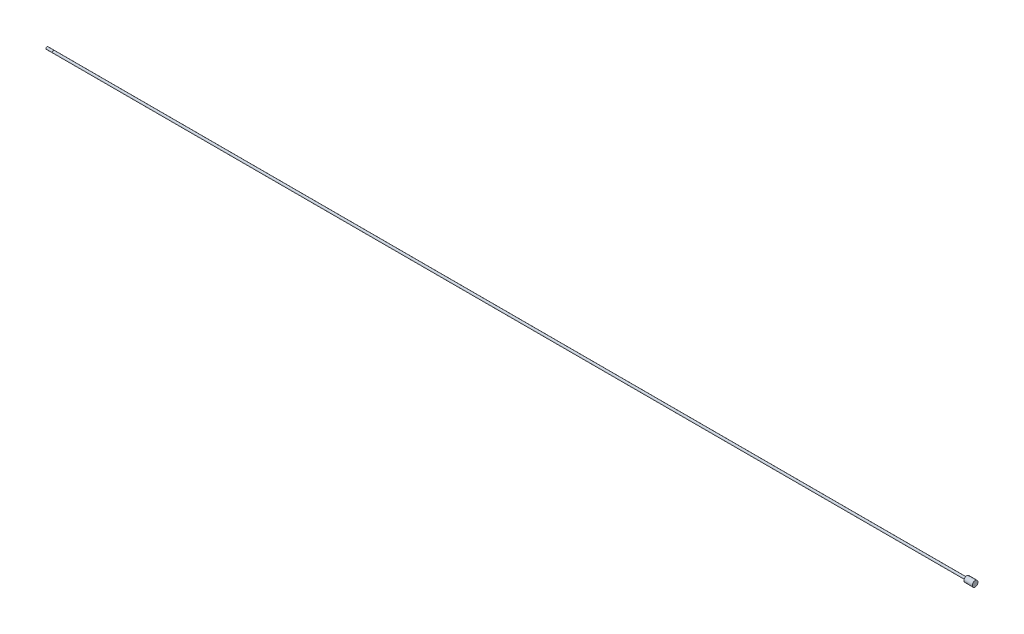
SolidWorks part; units mm, degrees
material "Plain Carbon Steel"
ref_plane "Front Plane" through (0, 0, 0) normal (0, 0, 1) x (1, 0, 0)
ref_plane "Top Plane" through (0, 0, 0) normal (0, 1, 0) x (1, 0, 0)
ref_plane "Right Plane" through (0, 0, 0) normal (1, 0, 0) x (0, 0, -1)
sketch "Sketch1" plane through (0, 0, 0) normal (0, 0, 1) x (1, 0, 0)
  line L0 (0, 0) -> (0, 1.5875)
  line L1 (0, 1.5875) -> (1291.463, 1.5875)
  line L2 (1291.463, 1.5875) -> (1291.463, 4.0323)
  line L3 (1291.463, 4.0323) -> (1303.2994, 4.0323)
  line L4 (1303.2994, 4.0323) -> (1303.2994, 0)
  line L5 (1303.2994, 0) -> (0, 0)
  line L6 (1303.2994, 0) -> (0, 0) construction
revolve "Revolve1" add sketch "Sketch1" angle 360 about L6 reverse direction yes
cosmetic thread "Cosmetic Thread1" parameters "D1"=9.652, "D2"=2.4181
sketch "Sketch2" plane through (0, 0, 0) normal (0, 0, 1) x (1, 0, 0)
  line L0 (-9.652, 0) -> (-9.652, 1.209)
  line L1 (-9.652, 1.209) -> (-9.2735, 1.5875)
  line L2 (-9.2735, 1.5875) -> (0, 1.5875)
  line L3 (0, 1.5875) -> (0, 0)
  line L4 (0, 0) -> (-9.652, 0)
  line L5 (0, 0) -> (-9.652, 0) construction
revolve "Revolve2" add sketch "Sketch2" angle 360 about L5 reverse direction yes
ref_plane "Plane1" through (0, 0, 0) normal (1, 0, 0) x (0, 0, -1)
ref_plane "Plane2" through (0, 0, 0) normal (1, 0, 0) x (0, 0, -1)
ref_plane "Plane3" through (2594.7624, 0, 0) normal (1, 0, 0) x (0, 0, -1)
ref_plane "Plane4" through (-9.652, 0, 0) normal (1, 0, 0) x (0, 0, -1)
sketch "Sketch3" plane through (0, 0, 0) normal (0, 0, 1) x (1, 0, 0)
  line L0 (-0.254, 1.8415) -> (-0.254, 1.3335)
  line L1 (-0.254, 1.3335) -> (0, 1.3335)
  line L2 (0, 1.3335) -> (0, 1.8415)
  line L3 (0, 1.8415) -> (-0.254, 1.8415)
  line L4 (0, 0) -> (-0.254, 0) construction
revolve "Cut-Revolve1" cut sketch "Sketch3" angle 360 about L4 reverse direction yes
ref_plane "Plane5" through (0, 0, 0) normal (1, 0, 0) x (0, 0, -1)
ref_plane "Plane6" through (0, 0, 0) normal (1, 0, 0) x (0, 0, -1)
ref_plane "Plane7" through (-9.652, 0, 0) normal (1, 0, 0) x (0, 0, -1)
ref_plane "dia1 XY" through (0, 0, 0) normal (1, 0, 0) x (0, 0, -1)
ref_plane "dia1 XZ" through (0, 1.5875, 0) normal (0, -1, 0) x (-1, 0, 0)
ref_plane "dia1 YZ" through (0, 0, 0) normal (0, 0, -1) x (-1, 0, 0)
ref_axis "dia1 X" through (0, 1.5875, 80.9) along (0, 0, -1)
ref_axis "dia1 Y" through (0, -50, 0) along (0, 1, 0)
ref_axis "dia1 Z" through (80.9, 1.5875, 0) along (-1, 0, 0)
sketch3d "dia1"
  point P0 (0, 1.5875, 0)
ref_plane "dia12 XY" through (0, 0, 0) normal (1, 0, 0) x (0, 0, -1)
ref_plane "dia12 XZ" through (0, 0, 0) normal (0, -1, 0) x (-1, 0, 0)
ref_plane "dia12 YZ" through (0, 0, 7.6835) normal (0, 0, -1) x (-1, 0, 0)
ref_axis "dia12 X" through (0, 0, 80.9) along (0, 0, -1)
ref_axis "dia12 Y" through (0, -50, 7.6835) along (0, 1, 0)
ref_axis "dia12 Z" through (80.9, 0, 7.6835) along (-1, 0, 0)
sketch3d "dia12"
  point P0 (0, 0, 7.6835)
ref_plane "dia1r XY" through (0, 0, 0) normal (1, 0, 0) x (0, 0, -1)
ref_plane "dia1r XZ" through (0, 0, 0) normal (0, -1, 0) x (-1, 0, 0)
ref_plane "dia1r YZ" through (0, 0, 5.5626) normal (0, 0, -1) x (-1, 0, 0)
ref_axis "dia1r X" through (0, 0, 80.9) along (0, 0, -1)
ref_axis "dia1r Y" through (0, -50, 5.5626) along (0, 1, 0)
ref_axis "dia1r Z" through (80.9, 0, 5.5626) along (-1, 0, 0)
sketch3d "dia1r"
  point P0 (0, 0, 5.5626)
ref_plane "dia2 XY" through (0, 0, 0) normal (1, 0, 0) x (0, 0, -1)
ref_plane "dia2 XZ" through (0, -1.5875, 0) normal (0, -1, 0) x (-1, 0, 0)
ref_plane "dia2 YZ" through (0, 0, 0) normal (0, 0, -1) x (-1, 0, 0)
ref_axis "dia2 X" through (0, -1.5875, 80.9) along (0, 0, -1)
ref_axis "dia2 Y" through (0, -50, 0) along (0, 1, 0)
ref_axis "dia2 Z" through (80.9, -1.5875, 0) along (-1, 0, 0)
sketch3d "dia2"
  point P0 (0, -1.5875, 0)
ref_plane "dia22 XY" through (0, 0, 0) normal (1, 0, 0) x (0, 0, -1)
ref_plane "dia22 XZ" through (0, 0, 0) normal (0, -1, 0) x (-1, 0, 0)
ref_plane "dia22 YZ" through (0, 0, -7.6835) normal (0, 0, -1) x (-1, 0, 0)
ref_axis "dia22 X" through (0, 0, 80.9) along (0, 0, -1)
ref_axis "dia22 Y" through (0, -50, -7.6835) along (0, 1, 0)
ref_axis "dia22 Z" through (80.9, 0, -7.6835) along (-1, 0, 0)
sketch3d "dia22"
  point P0 (0, 0, -7.6835)
ref_plane "dia2r XY" through (0, 0, 0) normal (1, 0, 0) x (0, 0, -1)
ref_plane "dia2r XZ" through (0, 0, 0) normal (0, -1, 0) x (-1, 0, 0)
ref_plane "dia2r YZ" through (0, 0, -5.5626) normal (0, 0, -1) x (-1, 0, 0)
ref_axis "dia2r X" through (0, 0, 80.9) along (0, 0, -1)
ref_axis "dia2r Y" through (0, -50, -5.5626) along (0, 1, 0)
ref_axis "dia2r Z" through (80.9, 0, -5.5626) along (-1, 0, 0)
sketch3d "dia2r"
  point P0 (0, 0, -5.5626)
ref_plane "rl1 XY" through (-9.652, 0, 0) normal (1, 0, 0) x (0, 0, -1)
ref_plane "rl1 XZ" through (0, 0, 0) normal (0, -1, 0) x (-1, 0, 0)
ref_plane "rl1 YZ" through (0, 0, 0) normal (0, 0, -1) x (-1, 0, 0)
ref_axis "rl1 X" through (-9.652, 0, 80.9) along (0, 0, -1)
ref_axis "rl1 Y" through (-9.652, -50, 0) along (0, 1, 0)
ref_axis "rl1 Z" through (80.9, 0, 0) along (-1, 0, 0)
sketch3d "rl1"
  point P0 (-9.652, 0, 0)
ref_plane "rl2 XY" through (0, 0, 0) normal (1, 0, 0) x (0, 0, -1)
ref_plane "rl2 XZ" through (0, 0, 0) normal (0, -1, 0) x (-1, 0, 0)
ref_plane "rl2 YZ" through (0, 0, 0) normal (0, 0, -1) x (-1, 0, 0)
ref_axis "rl2 X" through (0, 0, 80.9) along (0, 0, -1)
ref_axis "rl2 Y" through (0, -50, 0) along (0, 1, 0)
ref_axis "rl2 Z" through (80.9, 0, 0) along (-1, 0, 0)
sketch3d "rl2"
  point P0 (0, 0, 0)
ref_plane "rod_cp XY" through (0, 0, 0) normal (1, 0, 0) x (0, 0, -1)
ref_plane "rod_cp XZ" through (0, 0, 0) normal (0, -1, 0) x (-1, 0, 0)
ref_plane "rod_cp YZ" through (0, 0, 0) normal (0, 0, -1) x (-1, 0, 0)
ref_axis "rod_cp X" through (0, 0, 80.9) along (0, 0, -1)
ref_axis "rod_cp Y" through (0, -50, 0) along (0, 1, 0)
ref_axis "rod_cp Z" through (80.9, 0, 0) along (-1, 0, 0)
sketch3d "rod_cp"
  point P0 (0, 0, 0)
ref_plane "thd1 XY" through (-9.652, 0, 0) normal (1, 0, 0) x (0, 0, -1)
ref_plane "thd1 XZ" through (0, 1.5875, 0) normal (0, -1, 0) x (-1, 0, 0)
ref_plane "thd1 YZ" through (0, 0, 0) normal (0, 0, -1) x (-1, 0, 0)
ref_axis "thd1 X" through (-9.652, 1.5875, 80.9) along (0, 0, -1)
ref_axis "thd1 Y" through (-9.652, -50, 0) along (0, 1, 0)
ref_axis "thd1 Z" through (80.9, 1.5875, 0) along (-1, 0, 0)
sketch3d "thd1"
  point P0 (-9.652, 1.5875, 0)
ref_plane "thd2 XY" through (-9.652, 0, 0) normal (1, 0, 0) x (0, 0, -1)
ref_plane "thd2 XZ" through (0, -1.5875, 0) normal (0, -1, 0) x (-1, 0, 0)
ref_plane "thd2 YZ" through (0, 0, 0) normal (0, 0, -1) x (-1, 0, 0)
ref_axis "thd2 X" through (-9.652, -1.5875, 80.9) along (0, 0, -1)
ref_axis "thd2 Y" through (-9.652, -50, 0) along (0, 1, 0)
ref_axis "thd2 Z" through (80.9, -1.5875, 0) along (-1, 0, 0)
sketch3d "thd2"
  point P0 (-9.652, -1.5875, 0)
ref_plane "to_rod_clevis XY" through (-9.652, 0, 0) normal (1, 0, 0) x (0, 0, -1)
ref_plane "to_rod_clevis XZ" through (0, 0, 0) normal (0, -1, 0) x (-1, 0, 0)
ref_plane "to_rod_clevis YZ" through (0, 0, 0) normal (0, 0, -1) x (-1, 0, 0)
ref_axis "to_rod_clevis X" through (-9.652, 0, 80.9) along (0, 0, -1)
ref_axis "to_rod_clevis Y" through (-9.652, -50, 0) along (0, 1, 0)
ref_axis "to_rod_clevis Z" through (80.9, 0, 0) along (-1, 0, 0)
sketch3d "to_rod_clevis"
  point P0 (-9.652, 0, 0)
